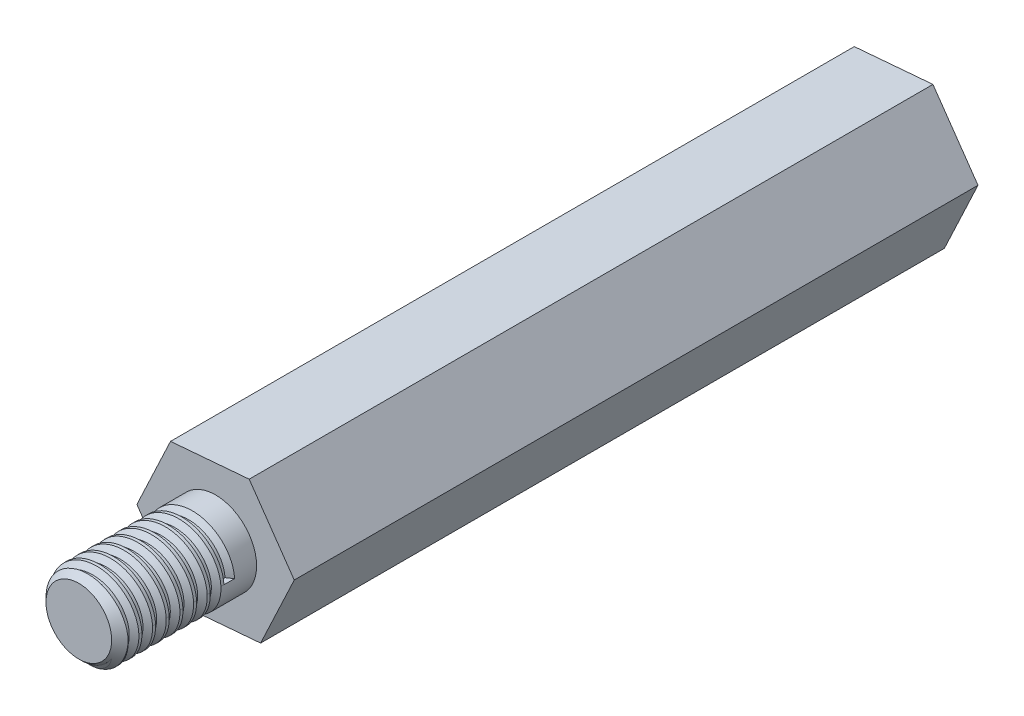
SolidWorks part; units mm, degrees
ref_plane "前视基准面" through (0, 0, 0) normal (0, 0, 1) x (1, 0, 0)
ref_plane "上视基准面" through (0, 0, 0) normal (0, 1, 0) x (1, 0, 0)
ref_plane "右视基准面" through (0, 0, 0) normal (1, 0, 0) x (0, 0, -1)
sketch "草图1" plane through (0, 0, 0) normal (0, 0, 1) x (1, 0, 0)
  line L1 (1.6473, -2.3706) -> (2.8766, 0.2414)
  line L2 (2.8766, 0.2414) -> (1.2293, 2.6119)
  line L3 (1.2293, 2.6119) -> (-1.6473, 2.3706)
  line L4 (-1.6473, 2.3706) -> (-2.8766, -0.2414)
  line L5 (-2.8766, -0.2414) -> (-1.2293, -2.6119)
  line L6 (-1.2293, -2.6119) -> (1.6473, -2.3706)
  circle A0 centre (0, 0) radius 1.5
  circle A1 centre (0, 0) radius 2.5 construction
  dimension "D1" = 3
  dimension "D2" = 5
extrude "凸台-拉伸1" add sketch "草图1" along normal blind 25 contours L5 L6 L1 L2 L3 L4 A0 | A0 region at (0.2025, -2.4138, 0)
hole_wizard "M3 螺纹孔1" positions "3D草图1" profile "草图2" tap size "M3" standard "GB"
sketch3d "3D草图1"
  point P0 (0, 0, 0)
  point P3 (0, 0, 0)
  point P5 (0, 0, 0)
  point P7 (0, 0, 0)
  point P9 (0, 0, 0)
sketch "草图2" plane through (0, 0, 0) normal (1, 0, 0) x (0, 1, 0)
  line L0 (0, 0) -> (0, 15.7511)
  line L1 (0, 15.7511) -> (1.25, 15)
  line L2 (1.25, 15) -> (1.25, 0)
  line L5 (1.25, 0) -> (0, 0)
  line L10 (0, 15.7511) -> (-1.25, 15) construction
  line L11 (0, -6.35) -> (0, 107.95) construction
  dimension "螺纹孔钻头直径" = 2.5
  dimension "螺纹孔钻头深度" = 15
  dimension "导头角度" = 118
cosmetic thread "孔螺蚊线1" parameters "D1"=10, "D2"=3
cosmetic thread "孔螺蚊线2" parameters "D1"=10, "D2"=3
cosmetic thread "孔螺蚊线3" parameters "D1"=10, "D2"=3
cosmetic thread "孔螺蚊线4" parameters "D1"=10, "D2"=3
cosmetic thread "孔螺蚊线5" parameters "D1"=10, "D2"=3
sketch "草图3" plane through (0, 0, 25) normal (0, 0, 1) x (1, 0, 0)
  circle A0 centre (0, 0) radius 1.5
  dimension "D1" = 3
extrude "凸台-拉伸2" add sketch "草图3" along normal blind 5
chamfer "倒角1" distance 0.3 angle 45 1 edges at (1.5, 0, 30)
sketch "草图4" plane through (0, 0, 30) normal (0, 0, 1) x (1, 0, 0)
  circle A0 centre (0, 0) radius 1.5 construction
  circle A1 centre (0, 0) radius 1.5
curve "螺旋线/涡状线1" pitch 0.5 height 4 radius 1.5 centre (0, 0, 30) axis (0, 0, -1) start towards (1, 0, 0)
sketch "草图5" plane through (0, 0, 0) normal (0, 1, 0) x (1, 0, 0)
  line L0 (1.5432, -30.225) -> (1.5432, -29.775)
  line L1 (1.5432, -29.775) -> (1.2932, -29.95)
  line L2 (1.2932, -29.95) -> (1.2932, -30.05)
  line L3 (1.2932, -30.05) -> (1.5432, -30.225)
  line L4 (1.2932, -30) -> (1.5984, -30) construction
  line L7 (-1.2, -30) -> (1.2, -30) construction
  line L8 (-1.2, -30) -> (1.2, -30) construction
  dimension "D1" = 0.45
  dimension "D2" = 0.1
  dimension "D3" = 0.25
sweep "切除-扫描2" cut profiles "草图5" path "螺旋线/涡状线1" align with end faces yes
